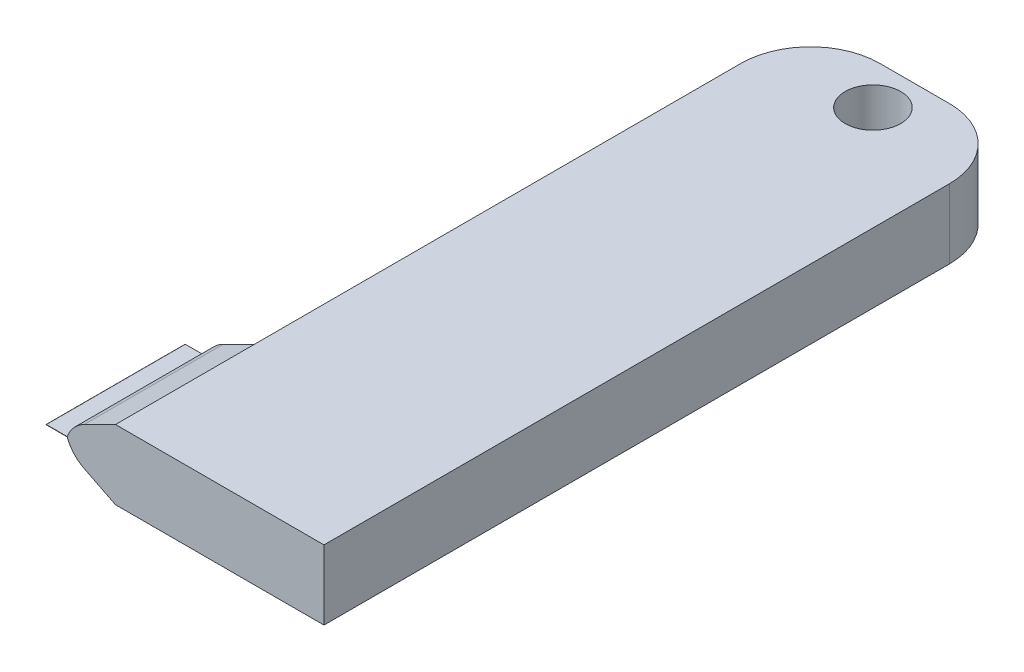
SolidWorks part; units mm, degrees
ref_plane "Front Plane" through (0, 0, 0) normal (0, 0, 1) x (1, 0, 0)
ref_plane "Top Plane" through (0, 0, 0) normal (0, 1, 0) x (1, 0, 0)
ref_plane "Right Plane" through (0, 0, 0) normal (1, 0, 0) x (0, 0, -1)
sketch "Sketch2" plane through (0, 0, 0) normal (0, 0, 1) x (1, 0, 0)
  line L1 (0, 0) -> (30, 0)
  line L2 (0, 0) -> (0, 10)
  line L3 (0, 10) -> (30, 10)
  line L4 (30, 0) -> (30, 10)
  dimension "D1" = 10
  dimension "D2" = 30
extrude "Boss-Extrude1" add sketch "Sketch2" along normal blind 100
sketch "Sketch3" plane through (0, 10, 0) normal (0, 1, 0) x (1, 0, 0)
  line L0 (30, 0) -> (0, 0) construction
  circle A0 centre (15, -6) radius 4
  point P2 (15, 0)
  dimension "D1" = 8
  dimension "D2" = 6
extrude "Cut-Extrude1" cut sketch "Sketch3" against normal blind 30
fillet "Fillet1" radius 10 1 edges at (30, 5, 0)
fillet "Fillet3" radius 10 1 edges at (0, 5, 0)
sketch "Sketch4" plane through (0, 0, 0) normal (-1, 0, 0) x (0, 0, 1)
  line L0 (100, 0) -> (10, 0) construction
  line L1 (80, 0) -> (100, 0)
  line L2 (80, 0) -> (80, 10)
  line L3 (80, 10) -> (100, 10)
  line L4 (100, 0) -> (100, 10)
  dimension "D1" = 20
extrude "Boss-Extrude2" add sketch "Sketch4" along normal blind 10
sketch "Sketch5" plane through (0, 0, 80) normal (0, 0, -1) x (-1, 0, 0)
  line L0 (0, 10) -> (10, 5)
  line L1 (10, 10) -> (10, 0) construction
  line L2 (10, 5) -> (10, 10)
  line L3 (10, 10) -> (0, 10)
  line L4 (10, 5) -> (0, 0)
  line L5 (0, 0) -> (10, 0)
  line L6 (10, 0) -> (10, 5)
  line M9 (10, 0) -> (10, 10)
  line M10 (10, 10) -> (0, 10)
extrude "Cut-Extrude2" cut sketch "Sketch5" against normal through all contours L0 M10 M9 | L4 L5 L6 region at (-6.6667, 8.3333, 80)
sketch "Sketch6" plane through (0, 0, 80) normal (0, 0, -1) x (-1, 0, 0)
  line L0 (6.9553, 6.5224) -> (6.9553, 5.0224)
  line L1 (0, 10) -> (10, 5) construction
  line L2 (6.9553, 5.0224) -> (9.9553, 5.0224)
  line L3 (9.9553, 5.0224) -> (6.9553, 6.5224)
  line L4 (10, 5) -> (6.2267, 5) construction
  line L5 (6.9553, 4.9776) -> (9.9553, 4.9776)
  line L6 (6.9553, 3.4776) -> (6.9553, 4.9776)
  line L7 (9.9553, 4.9776) -> (6.9553, 3.4776)
  dimension "D1" = 1.5
  dimension "D2" = 0.05
extrude "Cut-Extrude3" cut sketch "Sketch6" against normal through all contours L5 L7 L6 | L3 L0 L2
fillet "Fillet4" radius 5 1 edges at (-6.9553, 6.5224, 90)
fillet "Fillet5" radius 5 1 edges at (-6.9553, 3.4776, 90)
